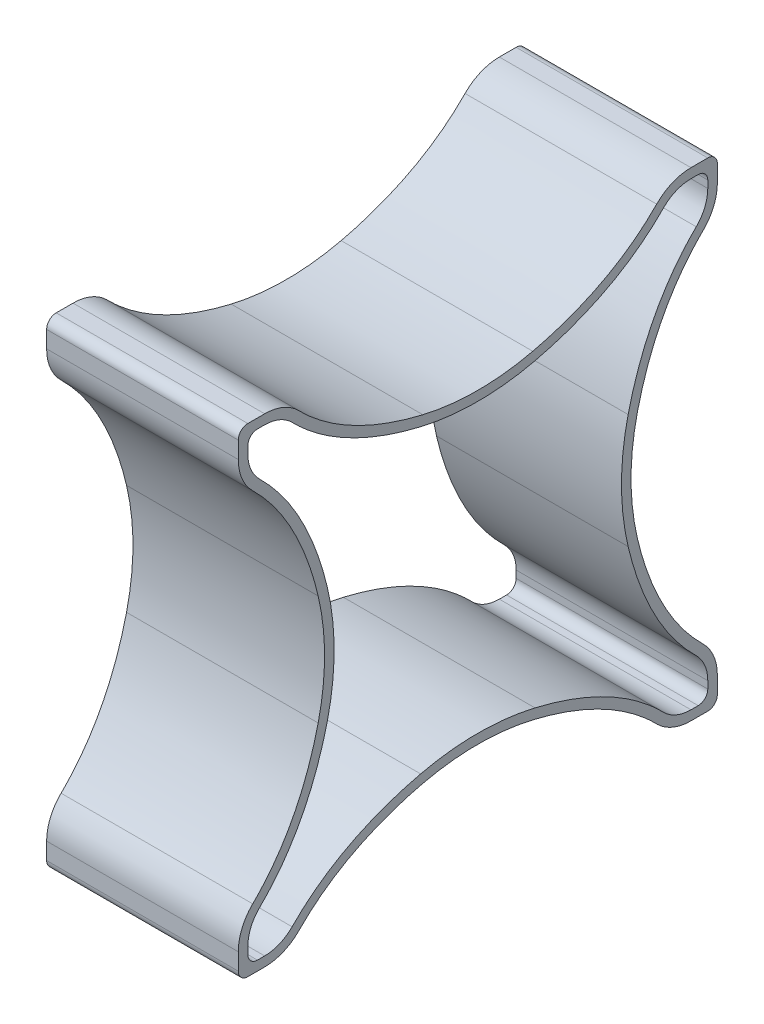
SolidWorks part; units mm, degrees
ref_plane "Front Plane" through (0, 0, 0) normal (0, 0, 1) x (1, 0, 0)
ref_plane "Top Plane" through (0, 0, 0) normal (0, 1, 0) x (1, 0, 0)
ref_plane "Right Plane" through (0, 0, 0) normal (1, 0, 0) x (0, 0, -1)
sketch "Sketch1" plane through (0, 0, 0) normal (1, 0, 0) x (0, 0, -1)
  line L0 (100, 0) -> (100, -5.5098)
  line L1 (0, 0) -> (100, 0) construction
  line L2 (0, 0) -> (0, -100) construction
  line L3 (0, -100) -> (100, -100) construction
  line L5 (2, -2) -> (2, -5.5098)
  line L6 (2, -98) -> (2, -94.4902)
  line L7 (100, -100) -> (100, -94.4902)
  line L8 (2, -98) -> (5.5098, -98)
  line L10 (0, 0) -> (5.5098, 0)
  line L11 (100, 0) -> (94.4902, 0)
  line L12 (100, -100) -> (94.4902, -100)
  line L13 (0, -100) -> (5.5098, -100)
  line L14 (0, -100) -> (0, -94.4902)
  line L15 (0, 0) -> (0, -5.5098)
  line L16 (98, -98) -> (94.4902, -98)
  line L17 (98, -98) -> (98, -94.4902)
  line L18 (98, -2) -> (98, -5.5098)
  line L19 (98, -2) -> (94.4902, -2)
  line L20 (2, -2) -> (5.5098, -2)
  arc A0 (96.9874, -12.6635) -> (100, -5.5098) centre (90, -5.5098) ccw
  arc A1 (96.9874, -87.3365) -> (100, -94.4902) centre (90, -94.4902) cw
  arc A2 (83.3208, -61.4746) -> (83.3208, -38.5254) centre (131.9863, -50) cw
  arc A3 (38.5254, -16.6792) -> (61.4746, -16.6792) centre (50, 31.9863) ccw
  arc A4 (12.6635, -3.0126) -> (5.5098, 0) centre (5.5098, -10) ccw
  arc A5 (87.3365, -3.0126) -> (94.4902, 0) centre (94.4902, -10) cw
  arc A6 (87.3365, -96.9874) -> (94.4902, -100) centre (94.4902, -90) ccw
  arc A7 (61.4746, -83.3208) -> (38.5254, -83.3208) centre (50, -131.9863) ccw
  arc A8 (12.6635, -96.9874) -> (5.5098, -100) centre (5.5098, -90) cw
  arc A9 (3.0126, -87.3365) -> (0, -94.4902) centre (10, -94.4902) ccw
  arc A10 (16.6792, -38.5254) -> (16.6792, -61.4746) centre (-31.9863, -50) cw
  arc A11 (3.0126, -12.6635) -> (0, -5.5098) centre (10, -5.5098) cw
  arc A12 (4.41, -11.2328) -> (2, -5.5098) centre (10, -5.5098) cw
  arc A13 (18.6258, -38.0664) -> (18.6258, -61.9336) centre (-31.9863, -50) cw
  arc A14 (4.41, -88.7672) -> (2, -94.4902) centre (10, -94.4902) ccw
  arc A15 (11.2328, -95.59) -> (5.5098, -98) centre (5.5098, -90) cw
  arc A16 (61.9336, -81.3742) -> (38.0664, -81.3742) centre (50, -131.9863) ccw
  arc A17 (88.7672, -95.59) -> (94.4902, -98) centre (94.4902, -90) ccw
  arc A18 (95.59, -88.7672) -> (98, -94.4902) centre (90, -94.4902) cw
  arc A19 (81.3742, -61.9336) -> (81.3742, -38.0664) centre (131.9863, -50) cw
  arc A20 (95.59, -11.2328) -> (98, -5.5098) centre (90, -5.5098) ccw
  arc A21 (88.7672, -4.41) -> (94.4902, -2) centre (94.4902, -10) cw
  arc A22 (38.0664, -18.6258) -> (61.9336, -18.6258) centre (50, 31.9863) ccw
  arc A23 (11.2328, -4.41) -> (5.5098, -2) centre (5.5098, -10) ccw
  spline S0 degree 3 poles (96.9874, -12.6635) (94.285, -15.3032) (88.726, -22.5012) (85.0016, -31.8334) (83.5063, -37.7385) (83.3208, -38.5254) knots 0.087568 0.087568 0.087568 0.087568 0.33605 0.688962 0.74236 0.74236 0.74236 0.74236
  spline S1 degree 3 poles (96.9874, -87.3365) (94.285, -84.6968) (88.726, -77.4988) (85.0016, -68.1666) (83.5063, -62.2615) (83.3208, -61.4746) knots 0.087568 0.087568 0.087568 0.087568 0.33605 0.688962 0.74236 0.74236 0.74236 0.74236
  spline S2 degree 3 poles (12.6635, -3.0126) (15.3032, -5.715) (22.5012, -11.274) (31.8334, -14.9984) (37.7385, -16.4937) (38.5254, -16.6792) knots 0.087568 0.087568 0.087568 0.087568 0.33605 0.688962 0.74236 0.74236 0.74236 0.74236
  spline S3 degree 3 poles (87.3365, -3.0126) (84.6968, -5.715) (77.4988, -11.274) (68.1666, -14.9984) (62.2615, -16.4937) (61.4746, -16.6792) knots 0.087568 0.087568 0.087568 0.087568 0.33605 0.688962 0.74236 0.74236 0.74236 0.74236
  spline S4 degree 3 poles (87.3365, -96.9874) (84.6968, -94.285) (77.4988, -88.726) (68.1666, -85.0016) (62.2615, -83.5063) (61.4746, -83.3208) knots 0.087568 0.087568 0.087568 0.087568 0.33605 0.688962 0.74236 0.74236 0.74236 0.74236
  spline S5 degree 3 poles (12.6635, -96.9874) (15.3032, -94.285) (22.5012, -88.726) (31.8334, -85.0016) (37.7385, -83.5063) (38.5254, -83.3208) knots 0.087568 0.087568 0.087568 0.087568 0.33605 0.688962 0.74236 0.74236 0.74236 0.74236
  spline S6 degree 3 poles (3.0126, -87.3365) (5.715, -84.6968) (11.274, -77.4988) (14.9984, -68.1666) (16.4937, -62.2615) (16.6792, -61.4746) knots 0.087568 0.087568 0.087568 0.087568 0.33605 0.688962 0.74236 0.74236 0.74236 0.74236
  spline S7 degree 3 poles (3.0126, -12.6635) (5.715, -15.3032) (11.274, -22.5012) (14.9984, -31.8334) (16.4937, -37.7385) (16.6792, -38.5254) knots 0.087568 0.087568 0.087568 0.087568 0.33605 0.688962 0.74236 0.74236 0.74236 0.74236
  spline S8 degree 1 poles (4.41, -11.2328) (18.6258, -38.0664) knots 0 0 1 1 construction
  spline S9 degree 1 poles (4.41, -88.7672) (18.6258, -61.9336) knots 0 0 1 1 construction
  spline S10 degree 1 poles (11.2328, -95.59) (38.0664, -81.3742) knots 0 0 1 1 construction
  spline S11 degree 1 poles (88.7672, -95.59) (61.9336, -81.3742) knots 0 0 1 1 construction
  spline S12 degree 1 poles (95.59, -88.7672) (81.3742, -61.9336) knots 0 0 1 1 construction
  spline S13 degree 1 poles (95.59, -11.2328) (81.3742, -38.0664) knots 0 0 1 1 construction
  spline S14 degree 1 poles (88.7672, -4.41) (61.9336, -18.6258) knots 0 0 1 1 construction
  spline S15 degree 1 poles (11.2328, -4.41) (38.0664, -18.6258) knots 0 0 1 1 construction
  spline S16 degree 3 poles (4.41, -11.2328) (5.3388, -12.14) (7.1194, -14.0455) (10.2989, -18.1041) (13.6193, -23.6203) (16.6303, -30.724) (18.0432, -35.5953) (18.6258, -38.0664) knots 0.087568 0.087568 0.087568 0.087568 0.169417 0.251266 0.414964 0.578662 0.74236 0.74236 0.74236 0.74236
  spline S17 degree 3 poles (18.6258, -61.9336) (18.0432, -64.4047) (16.6303, -69.276) (13.6193, -76.3797) (10.2989, -81.8959) (7.1194, -85.9545) (5.3388, -87.86) (4.41, -88.7672) knots 0.087568 0.087568 0.087568 0.087568 0.251266 0.414964 0.578662 0.660511 0.74236 0.74236 0.74236 0.74236
  spline S18 degree 3 poles (11.2328, -95.59) (12.14, -94.6612) (14.0455, -92.8806) (18.1041, -89.7011) (23.6203, -86.3807) (30.724, -83.3697) (35.5953, -81.9568) (38.0664, -81.3742) knots 0.087568 0.087568 0.087568 0.087568 0.169417 0.251266 0.414964 0.578662 0.74236 0.74236 0.74236 0.74236
  spline S19 degree 3 poles (61.9336, -81.3742) (64.4047, -81.9568) (69.276, -83.3697) (76.3797, -86.3807) (81.8959, -89.7011) (85.9545, -92.8806) (87.86, -94.6612) (88.7672, -95.59) knots 0.087568 0.087568 0.087568 0.087568 0.251266 0.414964 0.578662 0.660511 0.74236 0.74236 0.74236 0.74236
  spline S20 degree 3 poles (95.59, -88.7672) (94.6612, -87.86) (92.8806, -85.9545) (89.7011, -81.8959) (86.3807, -76.3797) (83.3697, -69.276) (81.9568, -64.4047) (81.3742, -61.9336) knots 0.087568 0.087568 0.087568 0.087568 0.169417 0.251266 0.414964 0.578662 0.74236 0.74236 0.74236 0.74236
  spline S21 degree 3 poles (81.3742, -38.0664) (81.9568, -35.5953) (83.3697, -30.724) (86.3807, -23.6203) (89.7011, -18.1041) (92.8806, -14.0455) (94.6612, -12.14) (95.59, -11.2328) knots 0.087568 0.087568 0.087568 0.087568 0.251266 0.414964 0.578662 0.660511 0.74236 0.74236 0.74236 0.74236
  spline S22 degree 3 poles (88.7672, -4.41) (87.86, -5.3388) (85.9545, -7.1194) (81.8959, -10.2989) (76.3797, -13.6193) (69.276, -16.6303) (64.4047, -18.0432) (61.9336, -18.6258) knots 0.087568 0.087568 0.087568 0.087568 0.169417 0.251266 0.414964 0.578662 0.74236 0.74236 0.74236 0.74236
  spline S23 degree 3 poles (38.0664, -18.6258) (35.5953, -18.0432) (30.724, -16.6303) (23.6203, -13.6193) (18.1041, -10.2989) (14.0455, -7.1194) (12.14, -5.3388) (11.2328, -4.41) knots 0.087568 0.087568 0.087568 0.087568 0.251266 0.414964 0.578662 0.660511 0.74236 0.74236 0.74236 0.74236
  dimension "D1" = 10
  dimension "D2" = 50
  dimension "D3" = 2
extrude "Boss-Extrude1" add sketch "Sketch1" along normal blind 40
fillet "Fillet1" radius 2 8 edges at (20, 0, 0) (20, -2, -2) (20, -100, 0) (20, -98, -2) (20, 0, -100) (20, -2, -98) (20, -100, -100) (20, -98, -98)
sketch "Sketch2" plane through (0, 0, 0) normal (-1, 0, 0) x (0, 0, 1)
  line L0 (-50, -20.0137) -> (-50, -79.9863) construction
  line L1 (-20.0137, -50) -> (-79.9863, -50) construction
ref_plane "Plane1" through (0, 0, -50) normal (0, 0, -1) x (0, -1, 0)
ref_plane "Plane2" through (0, -50, 0) normal (0, 1, 0) x (0, 0, -1)
ref_axis "Axis1" through (55, -50, -50) along (-1, 0, 0)
